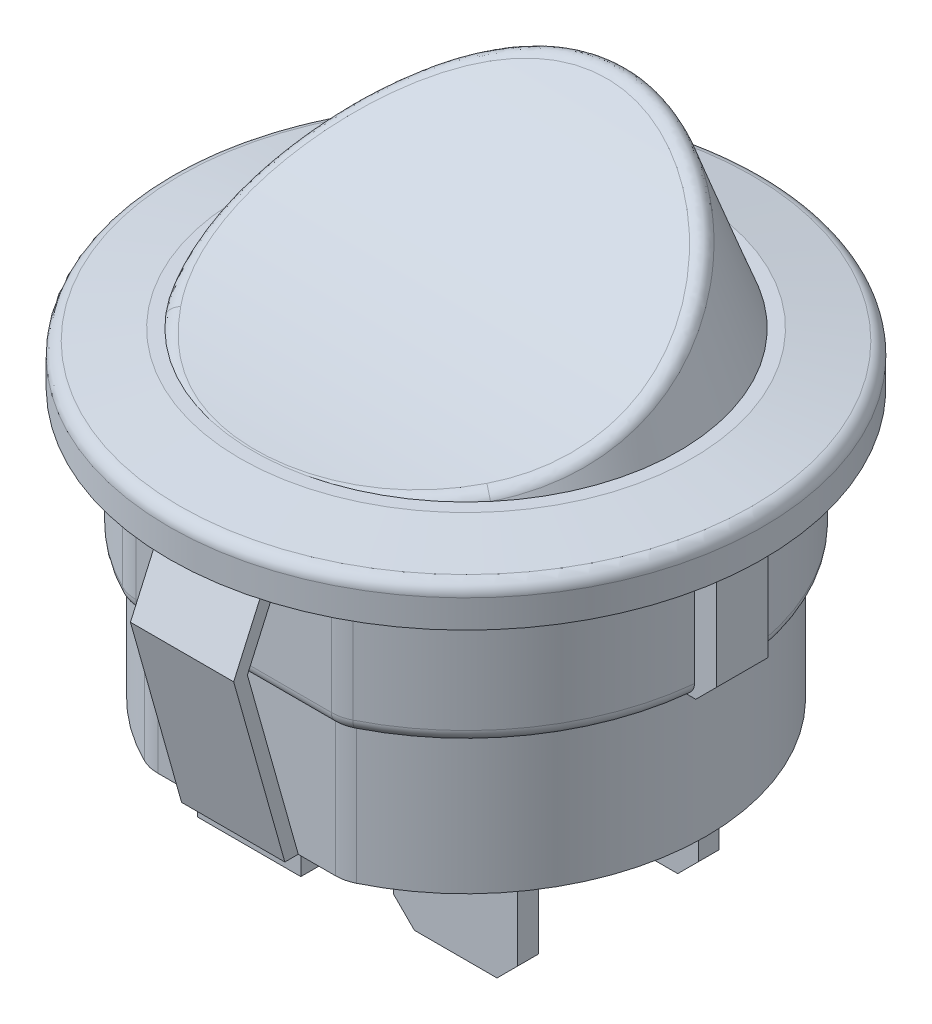
SolidWorks part; units mm, degrees
ref_plane "Front Plane" through (0, 0, 0) normal (0, 0, 1) x (1, 0, 0)
ref_plane "Top Plane" through (0, 0, 0) normal (0, 1, 0) x (1, 0, 0)
ref_plane "Right Plane" through (0, 0, 0) normal (1, 0, 0) x (0, 0, -1)
sketch "Sketch1" plane through (0, 0, 0) normal (0, 1, 0) x (1, 0, 0)
  line L0 (4.1243, -9) -> (-4.1243, -9)
  line L2 (-4.1243, 9) -> (4.1243, 9)
  arc A0 (-4.1243, 9) -> (-4.1243, -9) centre (0, 0) ccw
  arc A1 (4.1243, -9) -> (4.1243, 9) centre (0, 0) ccw
  dimension "D1" = 19.8
  dimension "D2" = 18
extrude "Boss-Extrude1" add sketch "Sketch1" against normal blind 5
sketch "Sketch2" plane through (0, 0, 0) normal (0, 1, 0) x (1, 0, 0)
  circle A0 centre (0, 0) radius 11.5
  dimension "D1" = 23
extrude "Boss-Extrude2" add sketch "Sketch2" along normal blind 2
chamfer "Chamfer1" distance 0.5 distance2 2.75 1 edges at (0, 2, 11.5) first distance on face at (0, 2, 11.5)
sketch "Sketch3" plane through (0, -5, 0) normal (0, -1, 0) x (1, 0, 0)
  line L0 (-3.7736, 8.5) -> (3.7736, 8.5)
  line L2 (3.7736, -8.5) -> (-3.7736, -8.5)
  arc A0 (3.7736, -8.5) -> (3.7736, 8.5) centre (0, 0) ccw
  arc A1 (-3.7736, 8.5) -> (-3.7736, -8.5) centre (0, 0) ccw
  dimension "D1" = 18.6
  dimension "D2" = 17
extrude "Boss-Extrude3" add sketch "Sketch3" along normal blind 5.4
sketch "Sketch4" plane through (0, -10.4, 0) normal (0, -1, 0) x (1, 0, 0)
  line L1 (-2.4, 0.4) -> (2.4, 0.4)
  line L2 (-2.4, 0.4) -> (-2.4, -0.4)
  line L3 (-2.4, -0.4) -> (2.4, -0.4)
  line L4 (2.4, 0.4) -> (2.4, -0.4)
  line L5 (-2.4, -6.6) -> (2.4, -6.6)
  line L6 (-2.4, -6.6) -> (-2.4, -7.4)
  line L7 (-2.4, -7.4) -> (2.4, -7.4)
  line L8 (2.4, -6.6) -> (2.4, -7.4)
  point P8 (0, 0.4)
  point P9 (0, 0)
  point P10 (0, -6.6)
  point P12 (-2.4, 0)
  point P13 (2.4, -7)
  point P14 (2.4, 0)
  dimension "D1" = 4.8
  dimension "D2" = 0.8
  dimension "D3" = 7
extrude "Boss-Extrude4" add sketch "Sketch4" along normal blind 8.4
sketch "Sketch5" plane through (0, 0, 0.4) normal (0, 0, 1) x (1, 0, 0)
  line L0 (2.4, -10.4) -> (-2.4, -10.4) construction
  line L1 (2.4, -12.9) -> (-2.4, -12.9) construction
  line L2 (-2.4, -18.8) -> (-2.4, -10.4) construction
  line L3 (2.4, -18.8) -> (2.4, -10.4) construction
  circle A0 centre (0, -15.4) radius 0.8
  circle A1 centre (-2.4, -12.9) radius 0.8
  circle A2 centre (2.4, -12.9) radius 0.8
  point P4 (0, -10.4)
  dimension "D1" = 1.6
  dimension "D2" = 5
  dimension "D3" = 2.5
extrude "Cut-Extrude1" cut sketch "Sketch5" against normal through all
sketch "Sketch6" plane through (0, 0, 0) normal (0, -1, 0) x (1, 0, 0)
  line L1 (10.7, 1) -> (8.8969, 1)
  line L2 (10.7, 1) -> (10.7, -1)
  line L3 (10.7, -1) -> (8.8969, -1)
  line L4 (8.8969, 1) -> (8.8969, -1)
  point P4 (10.7, 0)
  dimension "D1" = 2
  dimension "D2" = 10.7
extrude "Boss-Extrude5" add sketch "Sketch6" along normal up to vertex (5 mm away) up to point (4.1243, -5, -9)
chamfer "Chamfer2" distance 0.8 angle 45 1 edges at (10.7, -5, 0)
sketch "Sketch7" plane through (0, 0, 0) normal (1, 0, 0) x (0, 0, -1)
  line L0 (-9.5, 0) -> (-11, -3.3642)
  line L1 (-11, -3.3642) -> (-9.0181, -10.4)
  line L2 (-9.0181, -10.4) -> (-8.5, -10.4)
  line L3 (-9, 0) -> (-9, -0.1064)
  line L4 (-9, -0.1064) -> (-10.4697, -3.4027)
  line L5 (-9, 0) -> (-9.5, 0)
  line L6 (-9, 0) -> (9, 0) construction
  line L7 (-8.5, -10.4) -> (8.5, -10.4) construction
  line L8 (-10.4697, -3.4027) -> (-8.5, -10.3951)
  line L9 (-8.5, -10.3951) -> (-8.5, -10.4)
  dimension "D1" = 0.5
  dimension "D2" = 0.5
  dimension "D3" = 11
  dimension "D5" = 0.5
extrude "Boss-Extrude6" add sketch "Sketch7" along normal mid plane 4
mirror "Mirror1" about plane through (0, 0, 0) normal (0, 0, 1) of "Boss-Extrude6"
sketch "Sketch8" plane through (0, -10.4, 0) normal (0, -1, 0) x (1, 0, 0)
  line L0 (-2.4, -7.4) -> (2.4, -7.4) construction
  line L1 (2, -7.4) -> (-2, -7.4)
  line L2 (2, -7.4) -> (2, -8.4)
  line L3 (2, -8.4) -> (-2, -8.4)
  line L4 (-2, -7.4) -> (-2, -8.4)
  line L5 (-2.4, -0.4) -> (2.4, -0.4) construction
  line L6 (-2, -0.4) -> (2, -0.4)
  line L7 (-2, -0.4) -> (-2, -1.4)
  line L8 (-2, -1.4) -> (2, -1.4)
  line L9 (2, -0.4) -> (2, -1.4)
  line L10 (2.4, -6.6) -> (-2.4, -6.6) construction
  line L11 (-2, -6.6) -> (2, -6.6)
  line L12 (-2, -6.6) -> (-2, -5.6)
  line L13 (-2, -5.6) -> (2, -5.6)
  line L14 (2, -6.6) -> (2, -5.6)
  line L15 (2.4, 0.4) -> (-2.4, 0.4) construction
  line L16 (-2, 0.4) -> (2, 0.4)
  line L17 (-2, 0.4) -> (-2, 1.4)
  line L18 (-2, 1.4) -> (2, 1.4)
  line L19 (2, 0.4) -> (2, 1.4)
  line L20 (0, -6.6) -> (0, 6.6) construction
  line L21 (-2, 6.6) -> (2, 6.6)
  line L22 (-2, 6.6) -> (-2, 5.6)
  line L23 (-2, 5.6) -> (2, 5.6)
  line L24 (2, 6.6) -> (2, 5.6)
  line L25 (-2, 7.4) -> (2, 7.4)
  line L26 (-2, 7.4) -> (-2, 8.4)
  line L27 (-2, 8.4) -> (2, 8.4)
  line L28 (2, 7.4) -> (2, 8.4)
  line L29 (2, -7.4) -> (-2, 7.4) construction
  point P32 (0, -6.6)
  point P33 (0, -7.4)
  point P34 (0, -0.4)
  point P35 (0, 0.4)
  point P36 (0, 5.6)
  point P37 (0, 7.4)
  point P38 (0, 0)
  dimension "D1" = 4
  dimension "D2" = 1
extrude "Boss-Extrude7" add sketch "Sketch8" along normal blind 0.8
chamfer "Chamfer3" distance 0.8 angle 45 4 edges at (-2.4, -18.8, 0) (-2.4, -18.8, -7) (2.4, -18.8, -7) (2.4, -18.8, 0)
sketch "Sketch9" plane through (0, 2, 0) normal (0, 1, 0) x (1, 0, 0)
  circle A0 centre (0, 0) radius 8.25
  dimension "D1" = 16.5
extrude "Boss-Extrude8" add sketch "Sketch9" along normal blind 6.2 draft 20
sketch "Sketch10" plane through (0, 0, 0) normal (1, 0, 0) x (0, 0, -1)
  line L0 (8.75, 2) -> (-8.75, 2) construction
  circle A0 centre (-8.75, 22.6296) radius 20.6296
extrude "Cut-Extrude3" cut sketch "Sketch10" against normal mid plane 30
fillet "Fillet2" radius 1.5 8 edges at (4.1243, -2.5, 9) (-4.1243, -2.5, 9) (-4.1243, -2.5, -9) (4.1243, -2.5, -9) (3.7736, -7.7, -8.5) (3.7736, -7.7, 8.5) (-3.7736, -7.7, 8.5) (-3.7736, -7.7, -8.5)
fillet "Fillet4" radius 0.5 9 edges at (8.1573, -5, -5.6097) (4.13, -5, -8.9593) (0, -5, -9) (-4.13, -5, -8.9593) (8.1573, -5, 5.6097) (4.13, -5, 8.9593) (0, -5, 9) (-4.13, -5, 8.9593) (-9.9, -5, 0)
fillet "Fillet5" radius 0.5 1 edges at (4.7801, 2.1044, 6.6774)
fillet "Fillet6" radius 0.5 1 edges at (0, 1.5, 11.5)
